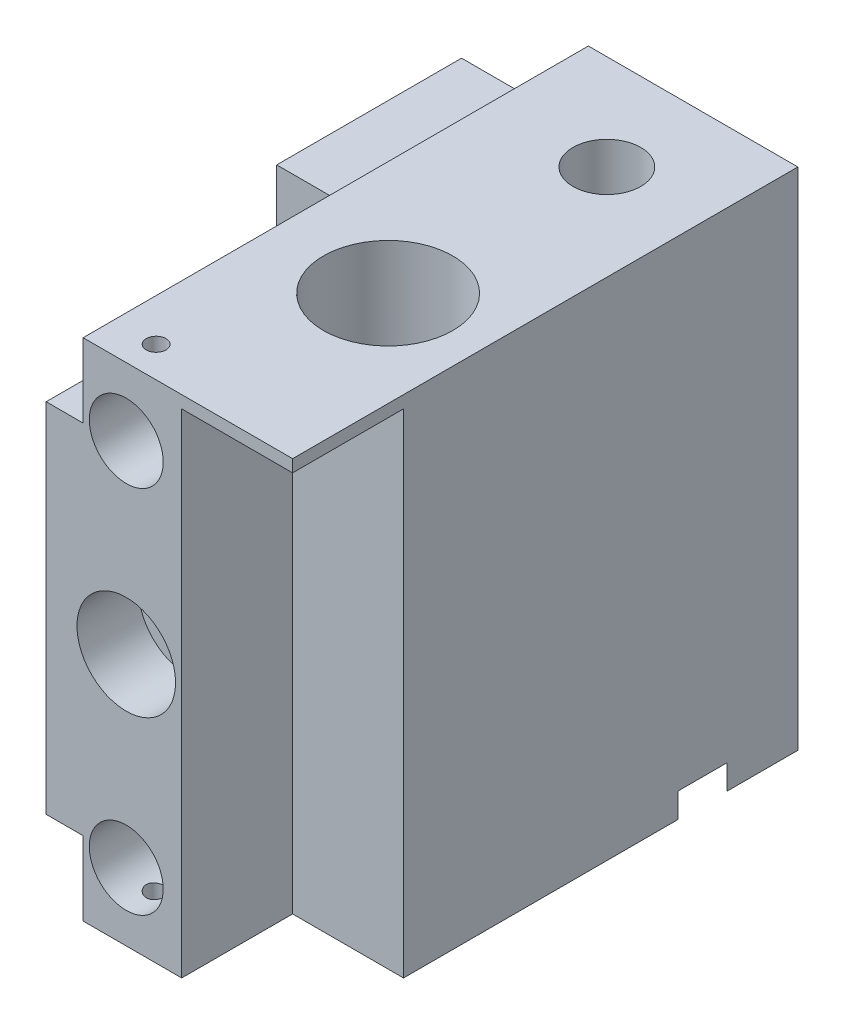
SolidWorks part; units mm, degrees
material "1060 Alloy"
ref_plane "Front Plane" through (0, 0, 0) normal (0, 0, 1) x (1, 0, 0)
ref_plane "Top Plane" through (0, 0, 0) normal (0, 1, 0) x (1, 0, 0)
ref_plane "Right Plane" through (0, 0, 0) normal (1, 0, 0) x (0, 0, -1)
sketch "Sketch1" plane through (0, 0, 0) normal (0, 0, 1) x (1, 0, 0)
  line L0 (-27, -17) -> (-27, -65) construction
  line L1 (0, 0) -> (-40, 0)
  line L2 (0, 0) -> (0, -82)
  line L3 (0, -82) -> (-40, -82)
  line L4 (-40, 0) -> (-40, -82)
  circle A0 centre (-27, -41) radius 5.5
  circle A1 centre (-27, -11) radius 6
  circle A2 centre (-27, -71) radius 6
  dimension "D3" = 11
  dimension "D4" = 12
  dimension "D5" = 12
  dimension "D1" = 40
  dimension "D2" = 82
  dimension "D6" = 11
  dimension "D7" = 30
  dimension "D8" = 13
  dimension "D9" = 30
  dimension "D10" = 11
extrude "Boss-Extrude1" add sketch "Sketch1" along normal blind 12
sketch "Sketch2" plane through (0, 0, 0) normal (0, 0, -1) x (-1, 0, 0)
  line L0 (0, -82) -> (0, 0) construction
  line L1 (40, -82) -> (0, -82) construction
  line L2 (40, 0) -> (40, -82) construction
  line L3 (0, 0) -> (40, 0) construction
  line L4 (0, -82) -> (0, 0)
  line L5 (40, -82) -> (0, -82)
  line L6 (40, 0) -> (40, -82)
  line L7 (0, 0) -> (40, 0)
  circle A0 centre (27, -41) radius 5.5 construction
  circle A1 centre (27, -41) radius 5.5
extrude "Boss-Extrude2" add sketch "Sketch2" along normal blind 70
sketch "Sketch3" plane through (0, 0, 0) normal (0, 1, 0) x (1, 0, 0)
  line L0 (-40, -5) -> (0, -5) construction
  line L1 (-40, -12) -> (-40, 70) construction
  line L2 (0, -12) -> (0, 70) construction
  line L3 (0, -12) -> (-40, -12) construction
  circle A0 centre (-27.1548, -7) radius 1.6
  dimension "D1" = 3.2
  dimension "D2" = 5
  dimension "D3" = 13
extrude "Cut-Extrude1" cut sketch "Sketch3" against normal blind 10
sketch "Sketch4" plane through (0, -82, 0) normal (0, -1, 0) x (1, 0, 0)
  circle A1 centre (-27.1548, 7) radius 1.6
  circle A2 centre (-27.1548, 7) radius 1.6
  dimension "D1" = 0
extrude "Cut-Extrude2" cut sketch "Sketch4" against normal blind 10
sketch "Sketch5" plane through (0, 0, 0) normal (0, 1, 0) x (1, 0, 0)
  line L0 (-15.5, 70) -> (-15.5, 49) construction
  line L1 (-40, 70) -> (0, 70) construction
  line L2 (0, -12) -> (-40, -12) construction
  line L3 (0, -12) -> (0, 70) construction
  line L4 (-15.5, 60) -> (-15.5, 49) construction
  line L5 (-15.5, 29.5) -> (-15.5, 8.5) construction
  line L6 (-15.5, 29.5) -> (-15.5, -12) construction
  circle A1 centre (-15.5, 19) radius 10.5
  circle A2 centre (-15.5, 54.5) radius 5.5
  dimension "D2" = 11
  dimension "D3" = 25
  dimension "D4" = 21
  dimension "D1" = 15.5
  dimension "D6" = 51
extrude "Cut-Extrude3" cut sketch "Sketch5" against normal blind 100
sketch "Sketch6" plane through (0, -82, 0) normal (0, 1, 0) x (1, 0, 0)
  circle A0 centre (-15.5, 54.5) radius 16
  dimension "D1" = 32
extrude "Cut-Extrude4" cut sketch "Sketch6" along normal blind 4
sketch "Sketch19" plane through (0, -78, 0) normal (0, -1, 0) x (-1, 0, 0)
  circle A0 centre (15.5, 54.5) radius 8.05
  dimension "D1" = 16.1
extrude "Cut-Extrude17" cut sketch "Sketch19" against normal blind 16
sketch "Sketch12" plane through (0, -78, 0) normal (0, -1, 0) x (-1, 0, 0)
  line L1 (26.8198, 50.5172) -> (30.8026, 61.837) construction
  line L2 (30.8026, 61.837) -> (19.4828, 65.8198) construction
  line L3 (4.1802, 58.4828) -> (0.1974, 47.163) construction
  line L4 (0.1974, 47.163) -> (11.5172, 43.1802) construction
  circle A0 centre (15.5, 54.5) radius 12 construction
  circle A1 centre (11.5172, 43.1802) radius 1.2
  circle A2 centre (26.8198, 50.5172) radius 1.2
  circle A3 centre (19.4828, 65.8198) radius 1.2
  circle A4 centre (4.1802, 58.4828) radius 1.2
  dimension "D1" = 24
  dimension "D2" = 2.4
extrude "Cut-Extrude12" cut sketch "Sketch12" against normal blind 12
sketch "Sketch13" plane through (0, 0, -70) normal (0, 0, -1) x (-1, 0, 0)
  line L1 (40, 0) -> (60, 0)
  line L2 (40, 0) -> (40, -70)
  line L3 (40, -70) -> (60, -70)
  line L4 (60, 0) -> (60, -70)
  dimension "D1" = 20
  dimension "D2" = 70
extrude "Boss-Extrude3" add sketch "Sketch13" against normal blind 30
sketch "Sketch15" plane through (0, 0, -70) normal (0, 0, -1) x (-1, 0, 0)
  line L0 (34, 0) -> (34, -12)
  line L1 (60, 0) -> (0, 0) construction
  line L2 (34, -12) -> (54.5811, -12)
  line L4 (34, -82) -> (34, -70)
  line L5 (0, -82) -> (11.5314, -82) construction
  line L6 (34, -70) -> (54.5811, -70)
  line L7 (54.5811, -70) -> (54.5811, -12)
  line L8 (34, 0) -> (77.5206, 0)
  line L9 (77.5206, 0) -> (77.5206, -82)
  line L10 (77.5206, -82) -> (34, -82)
  line L11 (60, -70) -> (60, 0) construction
  dimension "D1" = 26
  dimension "D2" = 58
  dimension "D3" = 12
  dimension "D4" = 12
extrude "Cut-Extrude14" cut sketch "Sketch15" against normal blind 115
sketch "Sketch22" plane through (0, -82, 0) normal (0, -1, 0) x (1, 0, 0)
  line L1 (0, 12) -> (-18, 12)
  line L2 (0, 12) -> (0, -6)
  line L3 (0, -6) -> (-18, -6)
  line L4 (-18, 12) -> (-18, -6)
  dimension "D1" = 18
  dimension "D2" = 18
extrude "Cut-Extrude18" cut sketch "Sketch22" against normal blind 80
sketch "Sketch23" plane through (0, 0, 12) normal (0, 0, 1) x (1, 0, 0)
  circle A0 centre (-27, -41) radius 8
  dimension "D1" = 16
extrude "Cut-Extrude19" cut sketch "Sketch23" against normal blind 10
sketch "Sketch24" plane through (0, 0, -70) normal (0, 0, -1) x (-1, 0, 0)
  circle A0 centre (27, -41) radius 10
extrude "Cut-Extrude20" cut sketch "Sketch24" against normal blind 2
sketch "Sketch25" plane through (0, 0, -70) normal (0, 0, -1) x (-1, 0, 0)
  circle A0 centre (3.5, -17.5) radius 2.5
  circle A1 centre (50.5, -17.5) radius 2.5
  circle A2 centre (50.5, -64.5) radius 2.5
  circle A3 centre (3.5, -64.5) radius 2.5
  dimension "D1" = 2
  dimension "D2" = 2
extrude "Cut-Extrude21" cut sketch "Sketch25" against normal blind 25
